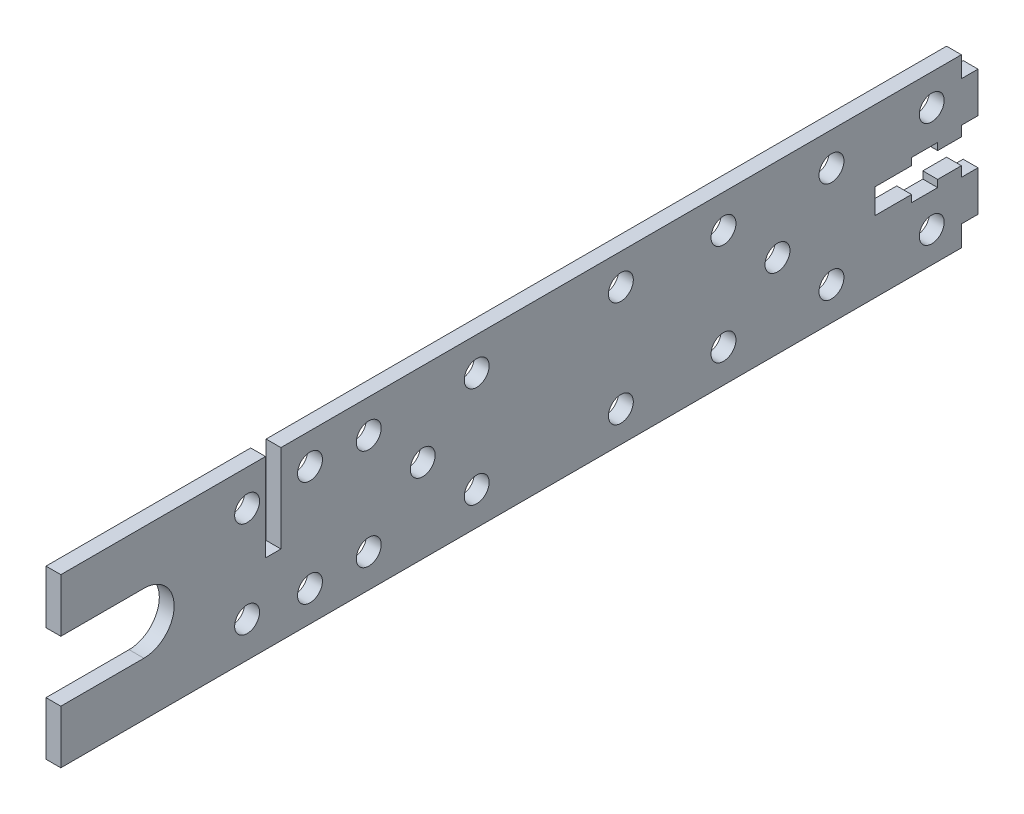
SolidWorks part; units mm, degrees
ref_plane "Front Plane" through (0, 0, 0) normal (0, 0, 1) x (1, 0, 0)
ref_plane "Top Plane" through (0, 0, 0) normal (0, 1, 0) x (1, 0, 0)
ref_plane "Right Plane" through (0, 0, 0) normal (1, 0, 0) x (0, 0, -1)
sketch "Sketch1" plane through (0, 0, 0) normal (1, 0, 0) x (0, 0, -1)
  line L0 (-98.171, 0) -> (98.171, 0) construction
  line L1 (-98.171, 17.907) -> (94.615, 17.907)
  line L2 (-98.171, 17.907) -> (-98.171, 6.477)
  line L3 (-98.171, -17.907) -> (94.615, -17.907)
  line L4 (98.171, 13.462) -> (98.171, 4.826)
  line L5 (94.615, 4.826) -> (94.615, 2.667)
  line L6 (94.615, -2.667) -> (94.615, -4.826)
  line L7 (94.615, 2.667) -> (89.535, 2.667)
  line L8 (94.615, 17.907) -> (94.615, 13.462)
  line L9 (94.615, -2.667) -> (89.535, -2.667)
  line L10 (76.073, 2.667) -> (76.073, -2.667)
  line L11 (86.741, 4.191) -> (86.741, -4.191) construction
  line L12 (-32.258, 10.795) -> (-9.144, 10.795) construction
  line L13 (83.947, 2.667) -> (76.073, 2.667)
  line L14 (89.535, 4.191) -> (83.947, 4.191)
  line L15 (89.535, 4.191) -> (89.535, 2.667)
  line L16 (89.535, -4.191) -> (83.947, -4.191)
  line L17 (83.947, 4.191) -> (83.947, 2.667)
  line L18 (66.802, 10.795) -> (43.688, 10.795) construction
  line L19 (66.802, -10.795) -> (43.688, -10.795) construction
  line L20 (83.947, -2.667) -> (76.073, -2.667)
  line L21 (89.535, -2.667) -> (89.535, -4.191)
  line L22 (83.947, -2.667) -> (83.947, -4.191)
  line L23 (98.171, -4.826) -> (98.171, -13.462)
  line L24 (98.171, 13.462) -> (94.615, 13.462)
  line L25 (98.171, 13.462) -> (98.171, 4.826)
  line L26 (98.171, 4.826) -> (94.615, 4.826)
  line L27 (-32.258, -10.795) -> (-9.144, -10.795) construction
  line L28 (98.171, 13.462) -> (94.615, 4.826) construction
  line L29 (98.171, 4.826) -> (94.615, 13.462) construction
  line L30 (-80.391, 6.477) -> (-98.171, 6.477)
  line L31 (98.171, -4.826) -> (94.615, -4.826)
  line L32 (-20.701, 10.795) -> (-20.701, -10.795) construction
  line L33 (98.171, -13.462) -> (94.615, -4.826) construction
  line L34 (98.171, -4.826) -> (94.615, -13.462) construction
  line L35 (98.171, -13.462) -> (94.615, -13.462)
  line L36 (-80.391, -6.477) -> (-98.171, -6.477)
  line L37 (-98.171, -6.477) -> (-98.171, -17.907)
  line L38 (94.615, -13.462) -> (94.615, -17.907)
  line L39 (55.245, 10.795) -> (55.245, -10.795) construction
  arc A0 (-80.391, -6.477) -> (-80.391, 6.477) centre (-80.391, 0) ccw
  circle A1 centre (-58.293, 10.287) radius 2.667
  circle A2 centre (-58.293, -10.287) radius 2.667
  circle A3 centre (-52.705, 0) radius 2.667
  circle A4 centre (-44.831, 11.303) radius 2.667
  circle A5 centre (21.717, 11.303) radius 2.667
  circle A6 centre (88.265, 11.303) radius 2.667
  circle A7 centre (88.265, -11.303) radius 2.667
  circle A8 centre (21.717, -11.303) radius 2.667
  circle A9 centre (-44.831, -11.303) radius 2.667
  circle A10 centre (-9.144, 10.795) radius 2.667
  circle A11 centre (-32.258, 10.795) radius 2.667
  circle A12 centre (66.802, 10.795) radius 2.667
  circle A13 centre (43.688, 10.795) radius 2.667
  circle A14 centre (43.688, -10.795) radius 2.667
  circle A15 centre (66.802, -10.795) radius 2.667
  circle A16 centre (-32.258, -10.795) radius 2.667
  circle A17 centre (-9.144, -10.795) radius 2.667
  circle A18 centre (-20.701, 0) radius 2.667
  circle A19 centre (55.245, 0) radius 2.667
  point P0 (0, 0)
  point P1 (86.741, 0)
  point P4 (0, 0)
  point P26 (96.393, 9.144)
  point P30 (96.393, -9.144)
  point P44 (76.073, 0)
  point P63 (55.245, 10.795)
  point P73 (-20.701, 10.795)
  dimension "D11" = 12.954
  dimension "D15" = 5.334
  dimension "D26" = 17.78
  dimension "D2" = 192.786
  dimension "D3" = 5.334
  dimension "D4" = 18.542
  dimension "D5" = 5.588
  dimension "D6" = 8.636
  dimension "D7" = 8.382
  dimension "D8" = 3.556
  dimension "D9" = 8.636
  dimension "D10" = 9.144
  dimension "D12" = 17.78
  dimension "D13" = 11.43
  dimension "D14" = 11.43
  dimension "D16" = 7.62
  dimension "D17" = 39.878
  dimension "D18" = 150.876
  dimension "D19" = 9.906
  dimension "D20" = 6.604
  dimension "D21" = 76.454
  dimension "D22" = 143.002
  dimension "D23" = 7.112
  dimension "D24" = 42.926
  dimension "D25" = 118.872
extrude "Boss-Extrude1" add sketch "Sketch1" along normal mid plane 3.175 contours A0 L36 L37 L3 L6 L9 L21 L16 L22 L20 L10 L13 L17 L14 L15 L7 L5 L26 L4 L24 L8 L1 L2 L30 A16 A14 A13 A12 A11 A10 A8 A2 A1 A3 A4 A5 | A3 region at (0, 0, -1.0471) region at (0, 0, 52.705)
sketch "Sketch2" plane through (1.5875, 0, 0) normal (1, 0, 0) x (0, 0, -1)
  line L0 (-98.171, 17.907) -> (94.615, 17.907) construction
  line L1 (-54.356, 17.907) -> (-51.054, 17.907)
  line L2 (-54.356, 17.907) -> (-54.356, -0.889)
  line L3 (-54.356, -0.889) -> (-51.054, -0.889)
  line L4 (-51.054, 17.907) -> (-51.054, -0.889)
  line L5 (-54.356, 17.907) -> (-51.054, -0.889) construction
  line L6 (-54.356, -0.889) -> (-51.054, 17.907) construction
  line L7 (98.171, -4.826) -> (98.171, -13.462) construction
  point P4 (-52.705, 8.509)
  point P9 (98.171, -9.144)
  dimension "D1" = 3.302
  dimension "D2" = 18.796
  dimension "D3" = 150.876
extrude "Cut-Extrude1" cut sketch "Sketch2" against normal through all
